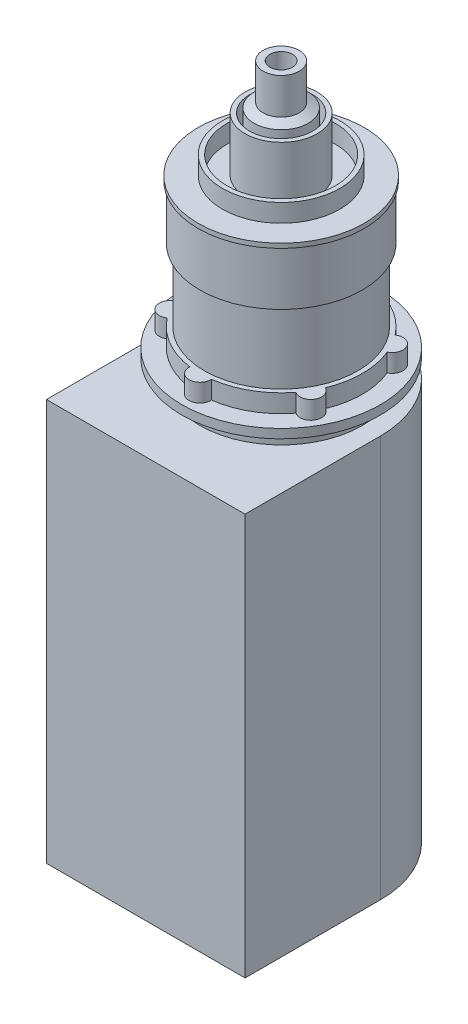
SolidWorks part; units mm, degrees
ref_plane "Front Plane" through (0, 0, 0) normal (0, 0, 1) x (1, 0, 0)
ref_plane "Top Plane" through (0, 0, 0) normal (0, 1, 0) x (1, 0, 0)
ref_plane "Right Plane" through (0, 0, 0) normal (1, 0, 0) x (0, 0, -1)
sketch "Sketch1" plane through (0, 0, 0) normal (0, 1, 0) x (1, 0, 0)
  line L0 (-34.925, 0) -> (34.925, 0)
  line L1 (-34.925, 0) -> (-34.925, 47.625)
  line L2 (34.925, 0) -> (34.925, 47.625)
  line L3 (34.925, 47.625) -> (-34.925, 47.625) construction
  line L4 (0, 85.4181) -> (0, -26.5122) construction
  arc A0 (-34.925, 47.625) -> (34.925, 47.625) centre (0, 47.625) cw
  point P8 (0, 0)
  dimension "D1" = 69.85
  dimension "D2" = 34.925
  dimension "D3" = 47.625
extrude "Boss-Extrude1" add sketch "Sketch1" along normal blind 139.7
shell "Shell1" thickness 1.5875 removed face at (0, 139.7, -32.5437)
sketch "Sketch2" plane through (0, 139.7, 0) normal (0, 1, 0) x (1, 0, 0)
  line L6 (34.925, 0) -> (34.925, 47.625) construction
  line L7 (-34.925, 0) -> (34.925, 0) construction
  line L8 (-34.925, 0) -> (-34.925, 47.625) construction
  line L9 (34.925, 0) -> (34.925, 47.625)
  line L10 (-34.925, 0) -> (34.925, 0)
  line L11 (-34.925, 0) -> (-34.925, 47.625)
  arc A2 (34.925, 47.625) -> (-34.925, 47.625) centre (0, 47.625) ccw construction
  arc A3 (34.925, 47.625) -> (-34.925, 47.625) centre (0, 47.625) ccw
extrude "Boss-Extrude2" add sketch "Sketch2" along normal blind 1.5875
sketch "Sketch3" plane through (0, 141.2875, 0) normal (0, 1, 0) x (1, 0, 0)
  circle A0 centre (0, 47.625) radius 28.575
  point P2 (0, 0)
  point P4 (0, 0)
  point P6 (0, 0)
  dimension "D1" = 57.15
extrude "Boss-Extrude3" add sketch "Sketch3" along normal blind 6.35
sketch "Sketch4" plane through (0, 147.6375, 0) normal (0, 1, 0) x (1, 0, 0)
  circle A0 centre (0, 47.625) radius 34.925
  dimension "D1" = 69.85
extrude "Boss-Extrude4" add sketch "Sketch4" along normal blind 3.175
sketch "Sketch5" plane through (0, 150.8125, 0) normal (0, 1, 0) x (1, 0, 0)
  arc A0 (-3.8015, 75.946) -> (-22.6259, 65.0777) centre (0, 47.625) ccw
  arc A1 (-3.8015, 75.946) -> (3.8015, 75.946) centre (0, 76.2) cw
  arc A2 (22.6259, 65.0777) -> (26.4275, 58.4933) centre (24.7467, 61.9125) cw
  arc A3 (26.4275, 36.7567) -> (22.6259, 30.1723) centre (24.7467, 33.3375) cw
  arc A4 (3.8015, 19.304) -> (-3.8015, 19.304) centre (0, 19.05) cw
  arc A5 (-22.6259, 30.1723) -> (-26.4275, 36.7567) centre (-24.7467, 33.3375) cw
  arc A6 (-26.4275, 58.4933) -> (-22.6259, 65.0777) centre (-24.7467, 61.9125) cw
  arc A7 (-26.4275, 58.4933) -> (-26.4275, 36.7567) centre (0, 47.625) ccw
  arc A8 (-22.6259, 30.1723) -> (-3.8015, 19.304) centre (0, 47.625) ccw
  arc A9 (3.8015, 19.304) -> (22.6259, 30.1723) centre (0, 47.625) ccw
  arc A10 (26.4275, 36.7567) -> (26.4275, 58.4933) centre (0, 47.625) ccw
  arc A11 (22.6259, 65.0777) -> (3.8015, 75.946) centre (0, 47.625) ccw
  dimension "D1" = 57.15
  dimension "D2" = 3.81
  dimension "D3" = 6
extrude "Boss-Extrude5" add sketch "Sketch5" along normal blind 6.35
sketch "Sketch6" plane through (0, 157.1625, 0) normal (0, 1, 0) x (1, 0, 0)
  circle A0 centre (0, 47.625) radius 26.9875
  dimension "D1" = 53.975
extrude "Boss-Extrude6" add sketch "Sketch6" along normal blind 25.4
sketch "Sketch8" plane through (0, 182.5625, 0) normal (0, 1, 0) x (1, 0, 0)
  circle A0 centre (0, 47.625) radius 28.575
  dimension "D1" = 57.15
extrude "Boss-Extrude7" add sketch "Sketch8" along normal blind 19.05
sketch "Sketch9" plane through (0, 201.6125, 0) normal (0, 1, 0) x (1, 0, 0)
  line L0 (34.925, 47.625) -> (-34.925, 47.625) construction
  circle A0 centre (0, 47.625) radius 29.21
  dimension "D1" = 58.42
extrude "Boss-Extrude8" add sketch "Sketch9" along normal blind 1.5875
sketch "Sketch10" plane through (0, 203.2, 0) normal (0, 1, 0) x (1, 0, 0)
  circle A0 centre (0, 47.625) radius 20.6375
  circle A1 centre (0, 47.625) radius 19.05
  dimension "D1" = 41.275
  dimension "D2" = 38.1
extrude "Boss-Extrude9" add sketch "Sketch10" along normal blind 6.35
sketch "Sketch12" plane through (0, 203.2, 0) normal (0, 1, 0) x (1, 0, 0)
  circle A0 centre (0, 47.625) radius 12.7
  circle A1 centre (0, 47.625) radius 11.1125
  dimension "D1" = 25.4
  dimension "D2" = 22.225
extrude "Boss-Extrude10" add sketch "Sketch12" along normal blind 19.05
sketch "Sketch14" plane through (0, 0, 0) normal (1, 0, 0) x (0, 0, -1)
  line L0 (47.625, 235.4929) -> (47.625, 105.0033) construction
  line L1 (47.625, 238.125) -> (53.975, 238.125)
  line L2 (53.975, 238.125) -> (53.975, 225.425)
  line L3 (53.975, 225.425) -> (57.15, 223.8375)
  line L4 (57.15, 223.8375) -> (57.15, 203.2)
  line L5 (58.7375, 203.2) -> (36.5125, 203.2) construction
  line L6 (57.15, 203.2) -> (47.625, 203.2)
  line L7 (47.625, 203.2) -> (47.625, 238.125)
  dimension "D1" = 47.625
  dimension "D2" = 6.35
  dimension "D3" = 34.925
  dimension "D4" = 20.6375
  dimension "D5" = 9.525
  dimension "D6" = 12.7
revolve "Revolve1" add sketch "Sketch14" angle 360 about L0
sketch "Sketch15" plane through (0, 238.125, 0) normal (0, 1, 0) x (1, 0, 0)
  circle A0 centre (0, 47.625) radius 3.9688
  dimension "D1" = 7.9375
extrude "Cut-Extrude1" cut sketch "Sketch15" against normal blind 19.05
equation "\"3.2.500in\"=3"
